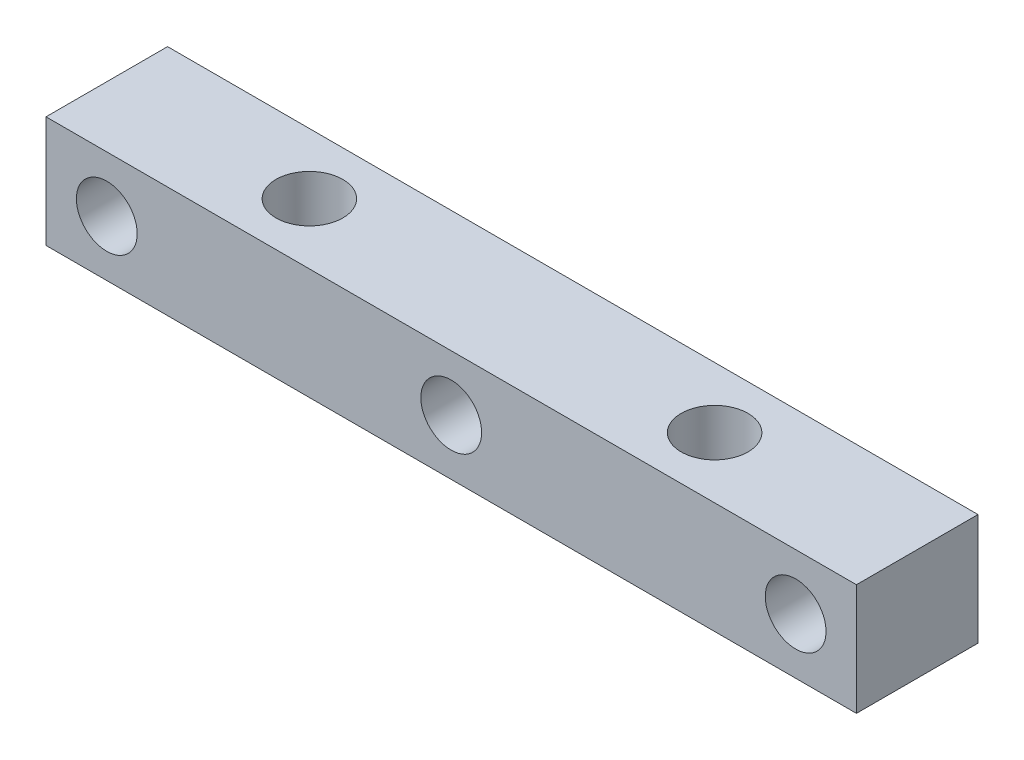
SolidWorks part; units mm, degrees
ref_plane "Front" through (0, 0, 0) normal (0, 0, 1) x (1, 0, 0)
ref_plane "Top" through (0, 0, 0) normal (0, 1, 0) x (1, 0, 0)
ref_plane "Right" through (0, 0, 0) normal (1, 0, 0) x (0, 0, -1)
sketch "Esquisse1" plane through (0, 0, 0) normal (0, 0, 1) x (1, 0, 0)
  line L1 (0, 0) -> (40, 0)
  line L2 (0, 0) -> (0, 5.5)
  line L3 (0, 5.5) -> (40, 5.5)
  line L4 (40, 0) -> (40, 5.5)
  dimension "D1" = 5.5
  dimension "D2" = 40
extrude "Boss.-Extru.1" add sketch "Esquisse1" along normal blind 6
sketch "Esquisse2" plane through (0, 0, 6) normal (0, 0, 1) x (1, 0, 0)
  line L0 (0, 2.75) -> (20, 2.75) construction
  line L1 (0, 5.5) -> (0, 0) construction
  line L2 (20, 2.75) -> (20, 5.5) construction
  line L3 (40, 5.5) -> (0, 5.5) construction
  circle A0 centre (20, 2.75) radius 1.5
  circle A1 centre (3, 2.75) radius 1.5
  circle A2 centre (37, 2.75) radius 1.5
  point P10 (4.1407, 3)
  dimension "D1" = 3
  dimension "D2" = 17
extrude "Enlèv. mat.-Extru.1" cut sketch "Esquisse2" against normal through all both and the other way through all
sketch "Esquisse3" plane through (0, 5.5, 0) normal (0, 1, 0) x (1, 0, 0)
  line L0 (40, -3) -> (0, -3) construction
  line L1 (40, -6) -> (40, 0) construction
  line L2 (0, -6) -> (0, 0) construction
  line L3 (20, -3) -> (20, 0) construction
  line L4 (40, 0) -> (0, 0) construction
  circle A0 centre (10, -3) radius 1.65
  circle A1 centre (30, -3) radius 1.65
  dimension "D1" = 3.3
  dimension "D2" = 20
extrude "Enlèv. mat.-Extru.2" cut sketch "Esquisse3" against normal through all both and the other way through all
